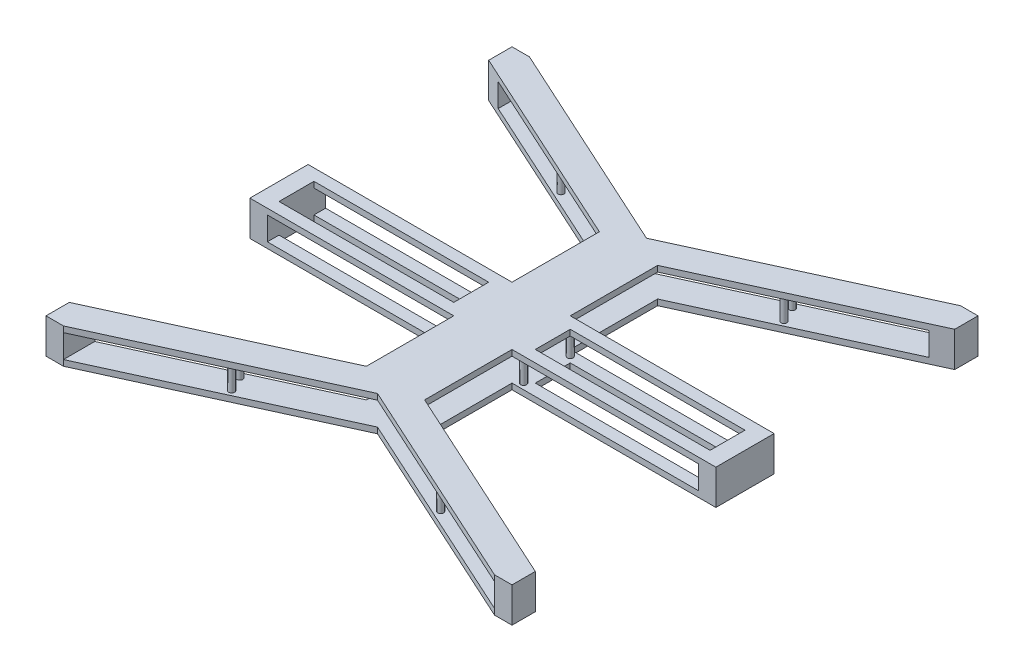
SolidWorks part; units mm, degrees
ref_plane "Front Plane" through (0, 0, 0) normal (0, 0, 1) x (1, 0, 0)
ref_plane "Top Plane" through (0, 0, 0) normal (0, 1, 0) x (1, 0, 0)
ref_plane "Right Plane" through (0, 0, 0) normal (1, 0, 0) x (0, 0, -1)
sketch "Sketch1" plane through (0, 0, 0) normal (0, 1, 0) x (1, 0, 0)
  line L1 (-13.2, 0) -> (13.2, 0) construction
  line L2 (80, 10) -> (80, -10)
  line L3 (80, -10) -> (10, -10)
  line L4 (10, -10) -> (10, -40)
  line L5 (10, -40) -> (80, -72)
  line L6 (80, -72) -> (80, -80)
  line L7 (80, -80) -> (74, -80)
  line L8 (74, -80) -> (0, -46.1714)
  line L9 (0, -13.2) -> (0, 13.2) construction
  line L11 (-80, 10) -> (-80, -10)
  line L12 (-80, -10) -> (-10, -10)
  line L13 (-10, -10) -> (-10, -40)
  line L14 (-10, -40) -> (-80, -72)
  line L15 (-80, -72) -> (-80, -80)
  line L16 (-80, -80) -> (-74, -80)
  line L17 (-74, -80) -> (0, -46.1714)
  line L18 (80, 10) -> (10, 10)
  line L19 (10, 10) -> (10, 40)
  line L20 (80, 80) -> (74, 80)
  line L21 (80, 72) -> (80, 80)
  line L22 (10, 40) -> (80, 72)
  line L23 (74, 80) -> (0, 46.1714)
  line L24 (-80, 72) -> (-80, 80)
  line L25 (-80, 80) -> (-74, 80)
  line L26 (-74, 80) -> (0, 46.1714)
  line L27 (-10, 40) -> (-80, 72)
  line L28 (-80, 10) -> (-10, 10)
  line L29 (-10, 10) -> (-10, 40)
  point P21 (80, 0)
  point P33 (-80, 0)
  dimension "D3" = 10
  dimension "D5" = 8
  dimension "D6" = 30
  dimension "D8" = 6
  dimension "D1" = 80
  dimension "D2" = 80
  dimension "D4" = 80
  dimension "D7" = 10
extrude "Boss-Extrude1" add sketch "Sketch1" along normal blind 6 and the other way blind 6
sketch "Sketch2" plane through (0, 0, 80) normal (0, 0, 1) x (1, 0, 0)
  line L0 (-74, -6) -> (-74, 6) construction
  line L1 (-74, -4) -> (74, -4)
  line L2 (-74, -4) -> (-74, 4)
  line L3 (-74, 4) -> (74, 4)
  line L4 (74, -4) -> (74, 4)
  line L5 (74, -6) -> (74, 6) construction
  line L7 (176, 0) -> (-176, 0) construction
  dimension "D1" = 4
  dimension "D2" = 4
extrude "Cut-Extrude1" cut sketch "Sketch2" against normal blind 160
sketch "Sketch4" plane through (0, 6, 0) normal (0, 1, 0) x (1, 0, 0)
  line L0 (-13.2, 0) -> (13.2, 0) construction
  line L1 (-74, 6) -> (-14, 6)
  line L2 (-74, 6) -> (-74, -6)
  line L3 (-74, -6) -> (-14, -6)
  line L4 (-14, 6) -> (-14, -6)
  line L5 (-80, 10) -> (-80, -10) construction
  line L7 (0, -13.2) -> (0, 13.2) construction
  line L8 (74, -6) -> (14, -6)
  line L9 (14, 6) -> (14, -6)
  line L10 (74, 6) -> (14, 6)
  line L11 (74, 6) -> (74, -6)
  dimension "D1" = 6
  dimension "D2" = 6
  dimension "D3" = 6
  dimension "D4" = 60
extrude "Cut-Extrude2" cut sketch "Sketch4" against normal blind 12
sketch "Sketch5" plane through (0, -4, 0) normal (0, 1, 0) x (1, 0, 0)
  line L1 (-10, -40) -> (-74, -69.2571) construction
  line L2 (-74, -80) -> (0, -46.1714) construction
  line L4 (-39.1032, -53.3043) -> (-35.0411, -62.1902) construction
  line L5 (0, -13.2) -> (0, 13.2) construction
  line L6 (-14, 6) -> (-14, -6) construction
  line L7 (-14, -6) -> (-74, -6) construction
  line L8 (-13.2, 0) -> (13.2, 0) construction
  circle A0 centre (-35.8726, -60.3713) radius 1
  circle A1 centre (-38.2717, -55.1233) radius 1
  circle A3 centre (-12, -8) radius 1
  circle A4 centre (0, -40.1714) radius 1
  circle A5 centre (12, -8) radius 1
  circle A6 centre (35.8726, -60.3713) radius 1
  circle A7 centre (38.2717, -55.1233) radius 1
  circle A8 centre (38.2717, 55.1233) radius 1
  circle A9 centre (35.8726, 60.3713) radius 1
  circle A10 centre (-35.8726, 60.3713) radius 1
  circle A11 centre (-38.2717, 55.1233) radius 1
  circle A12 centre (0, 40.1714) radius 1
  circle A13 centre (12, 8) radius 1
  circle A14 centre (-12, 8) radius 1
  dimension "D1" = 2
  dimension "D2" = 2
  dimension "D4" = 2
  dimension "D3" = 2
  dimension "D6" = 2
  dimension "D8" = 32
  dimension "D5" = 2
  dimension "D7" = 90
  dimension "D9" = 6
  dimension "D10" = 2
  dimension "D11" = 2
extrude "Boss-Extrude2" add sketch "Sketch5" along normal blind 8
equation "\"A\"= 2"
equation "\"D5@Sketch1\"=4*\"A\""
equation "\"D6@Sketch1\"=15*\"A\""
equation "\"D8@Sketch1\"=3*\"A\""
equation "\"D1@Sketch1\"=40*\"A\""
equation "\"D2@Sketch1\"=40*\"A\""
equation "\"D4@Sketch1\"=40*\"A\""
equation "\"D7@Sketch1\"=5*\"A\""
equation "\"D1@Boss-Extrude1\"=3*\"A\""
equation "\"D2@Boss-Extrude1\"=3*\"A\""
equation "\"D1@Sketch2\"=2*\"A\""
equation "\"D2@Sketch2\"=2*\"A\""
equation "\"D1@Sketch4\"=3*\"A\""
equation "\"D2@Sketch4\"=3*\"A\""
equation "\"D3@Sketch4\"=3*\"A\""
equation "\"D4@Sketch4\"=30*\"A\""
equation "\"D1@Cut-Extrude2\"=6*\"A\""
equation "\"D1@Cut-Extrude1\"=80*\"A\""
equation "\"D3@Sketch1\"=5*\"A\""
equation "\"D1@Sketch5\"=\"A\""
equation "\"D2@Sketch5\"=\"A\""
equation "\"D4@Sketch5\"=\"A\""
equation "\"D6@Sketch5\"=\"A\""
equation "\"D8@Sketch5\"=16*\"A\""
equation "\"D5@Sketch5\"=\"A\""
equation "\"D3@Sketch5\"=\"A\""
equation "\"D9@Sketch5\"=3*\"A\""
equation "\"D10@Sketch5\"=\"A\""
equation "\"D11@Sketch5\"=\"A\""
equation "\"D1@Boss-Extrude2\"=4*\"A\""
